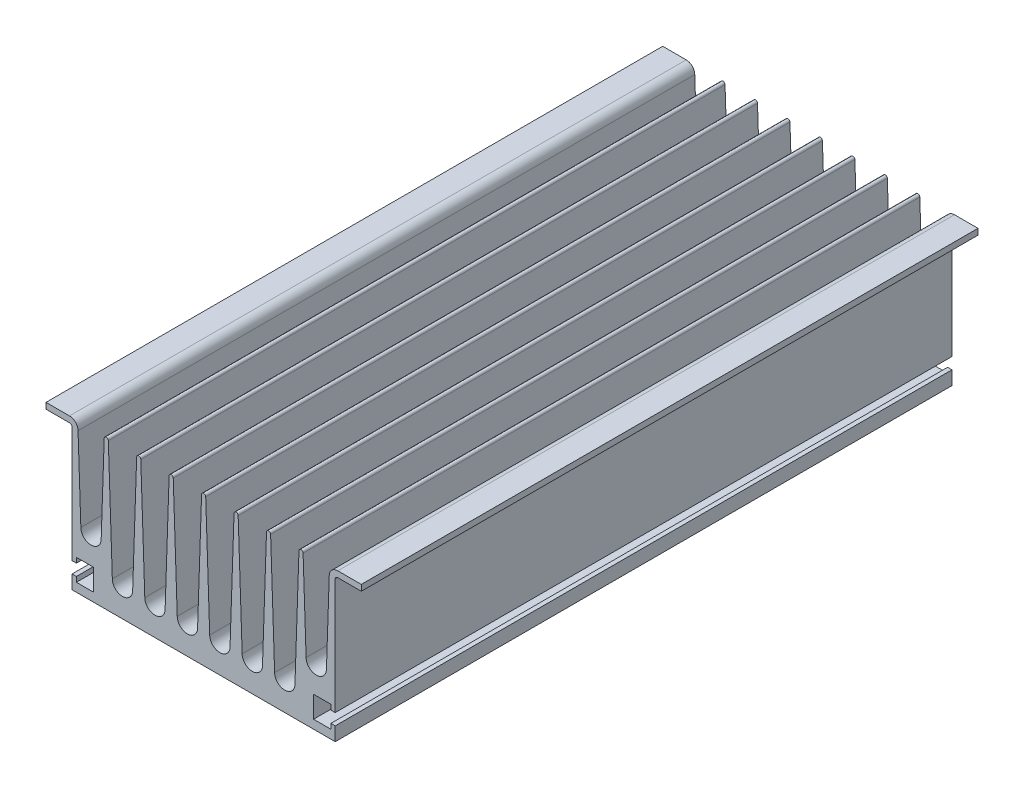
SolidWorks part; units mm, degrees
ref_plane "Plano frontal" through (0, 0, 0) normal (0, 0, 1) x (1, 0, 0)
ref_plane "Plano superior" through (0, 0, 0) normal (0, 1, 0) x (1, 0, 0)
ref_plane "Plano direito" through (0, 0, 0) normal (1, 0, 0) x (0, 0, -1)
sketch "Esboço1" plane through (0, 0, 0) normal (0, 0, 1) x (1, 0, 0)
  line L3 (0, 0) -> (-121.6, 0)
  line L47 (-121.6, 0) -> (-121.6, 6.35)
  line L49 (-121.6, 6.35) -> (-119.6, 6.35)
  line L51 (-119.6, 6.35) -> (-119.6, 4)
  line L53 (-119.6, 4) -> (-111.6, 4)
  line L55 (-111.6, 4) -> (-111.6, 14)
  line L57 (-111.6, 14) -> (-119.6, 14)
  line L61 (-119.6, 14) -> (-119.6, 11.65)
  line L65 (-119.6, 11.65) -> (-121.6, 11.65)
  line L97 (-121.6, 11.65) -> (-121.6, 65.056)
  line L98 (-122.7867, 66.2427) -> (-133.65, 66.2427)
  line L100 (-133.65, 66.2427) -> (-133.65, 69)
  line L101 (-133.65, 69) -> (-122.7867, 69)
  line L102 (-115.6, 14) -> (-115.6, 4) construction
  line L103 (-119.6, 11.65) -> (-119.6, 6.35) construction
  line L104 (-119.6, 9) -> (-115.6, 9) construction
  line L113 (-117.5473, 27) -> (-118.8427, 65.056)
  line L114 (-117.5473, 27) -> (-108.1473, 27) construction
  line L115 (-60.8, 0) -> (-60.8, 69) construction
  line L116 (-133.65, 69) -> (9.4418, 69) construction
  line L146 (-108.1473, 27) -> (-106.75, 68.05)
  line L147 (-104.85, 68.05) -> (-103, 13.7)
  line L148 (-106.75, 68.05) -> (-104.85, 68.05) construction
  line L149 (-122.7867, 66.2427) -> (-122.7867, 69) construction
  line L150 (-121.6, 65.056) -> (-118.8427, 65.056) construction
  line L151 (-105.8, 68.05) -> (-105.8, 0) construction
  line L152 (-105.8, 27) -> (-103.4527, 27) construction
  line L153 (-105.8, 27) -> (-108.1473, 27) construction
  line L154 (-93.6, 13.7) -> (-103, 13.7) construction
  line L155 (-93.6, 13.7) -> (-91.75, 68.05)
  line L156 (-89.85, 68.05) -> (-88, 13.7)
  line L161 (-91.75, 68.05) -> (-89.85, 68.05) construction
  line L162 (-78.6, 13.7) -> (-76.75, 68.05)
  line L163 (-88, 13.7) -> (-78.6, 13.7) construction
  line L164 (-76.75, 68.05) -> (-74.85, 68.05) construction
  line L165 (-74.85, 68.05) -> (-73, 13.7)
  line L166 (-63.6, 13.7) -> (-61.75, 68.05)
  line L167 (-61.75, 68.05) -> (-59.85, 68.05) construction
  line L168 (-73, 13.7) -> (-63.6, 13.7) construction
  line L169 (-122.7867, 66.2427) -> (-122.7867, 65.056) construction
  line L170 (-122.7867, 65.056) -> (-121.6, 65.056) construction
  line L171 (0, 0) -> (0, 6.35)
  line L172 (1.1867, 65.056) -> (0, 65.056) construction
  line L173 (1.1867, 66.2427) -> (1.1867, 65.056) construction
  line L174 (-48.6, 13.7) -> (-58, 13.7) construction
  line L175 (-44.85, 68.05) -> (-46.75, 68.05) construction
  line L176 (-33.6, 13.7) -> (-43, 13.7) construction
  line L177 (-29.85, 68.05) -> (-31.75, 68.05) construction
  line L178 (-28, 13.7) -> (-18.6, 13.7) construction
  line L179 (-15.8, 27) -> (-13.4527, 27) construction
  line L180 (-15.8, 27) -> (-18.1473, 27) construction
  line L181 (0, 65.056) -> (-2.7573, 65.056) construction
  line L182 (1.1867, 66.2427) -> (1.1867, 69) construction
  line L183 (-14.85, 68.05) -> (-16.75, 68.05) construction
  line L184 (-4.0527, 27) -> (-13.4527, 27) construction
  line L185 (-2, 9) -> (-6, 9) construction
  line L186 (-2, 11.65) -> (-2, 6.35) construction
  line L187 (-6, 14) -> (-6, 4) construction
  line L188 (-58, 13.7) -> (-59.85, 68.05)
  line L189 (-46.75, 68.05) -> (-48.6, 13.7)
  line L190 (-43, 13.7) -> (-44.85, 68.05)
  line L191 (-31.75, 68.05) -> (-33.6, 13.7)
  line L192 (-28, 13.7) -> (-29.85, 68.05)
  line L193 (-16.75, 68.05) -> (-18.6, 13.7)
  line L194 (-13.4527, 27) -> (-14.85, 68.05)
  line L195 (-4.0527, 27) -> (-2.7573, 65.056)
  line L196 (12.05, 69) -> (1.1867, 69)
  line L197 (12.05, 66.2427) -> (12.05, 69)
  line L198 (1.1867, 66.2427) -> (12.05, 66.2427)
  line L199 (0, 11.65) -> (0, 65.056)
  line L200 (-2, 11.65) -> (0, 11.65)
  line L201 (-2, 14) -> (-2, 11.65)
  line L202 (-10, 14) -> (-2, 14)
  line L203 (-10, 4) -> (-10, 14)
  line L204 (-2, 4) -> (-10, 4)
  line L205 (-2, 6.35) -> (-2, 4)
  line L206 (0, 6.35) -> (-2, 6.35)
  arc A1 (-121.6, 65.056) -> (-122.7867, 66.2427) centre (-122.7867, 65.056) ccw
  arc A2 (-118.8427, 65.056) -> (-122.7867, 69) centre (-122.7867, 65.056) ccw
  arc A3 (-117.5473, 27) -> (-108.1473, 27) centre (-112.8473, 27) ccw
  arc A4 (-106.75, 68.05) -> (-104.85, 68.05) centre (-105.8, 68.05) cw
  arc A5 (-93.6, 13.7) -> (-103, 13.7) centre (-98.3, 13.7) cw
  arc A6 (-91.75, 68.05) -> (-89.85, 68.05) centre (-90.8, 68.05) cw
  arc A7 (-88, 13.7) -> (-78.6, 13.7) centre (-83.3, 13.7) ccw
  arc A8 (-76.75, 68.05) -> (-74.85, 68.05) centre (-75.8, 68.05) cw
  arc A9 (-59.85, 68.05) -> (-61.75, 68.05) centre (-60.8, 68.05) ccw
  arc A10 (-73, 13.7) -> (-63.6, 13.7) centre (-68.3, 13.7) ccw
  arc A11 (-48.6, 13.7) -> (-58, 13.7) centre (-53.3, 13.7) cw
  arc A12 (-44.85, 68.05) -> (-46.75, 68.05) centre (-45.8, 68.05) ccw
  arc A13 (-33.6, 13.7) -> (-43, 13.7) centre (-38.3, 13.7) cw
  arc A14 (-29.85, 68.05) -> (-31.75, 68.05) centre (-30.8, 68.05) ccw
  arc A15 (-28, 13.7) -> (-18.6, 13.7) centre (-23.3, 13.7) ccw
  arc A16 (-14.85, 68.05) -> (-16.75, 68.05) centre (-15.8, 68.05) ccw
  arc A17 (-4.0527, 27) -> (-13.4527, 27) centre (-8.7527, 27) cw
  arc A18 (-2.7573, 65.056) -> (1.1867, 69) centre (1.1867, 65.056) cw
  arc A19 (0, 65.056) -> (1.1867, 66.2427) centre (1.1867, 65.056) cw
  point P24 (-123.4226, 69.701)
  point P43 (-118.817, 64.3035)
  point P50 (-88, 13.7)
  point P55 (-133.65, 67.6213)
  point P56 (-123.5004, 69.988)
  point P57 (0, 0)
  dimension "D7" = 42
  dimension "D9" = 4.7
  dimension "D10" = 13.7
  dimension "D11" = 72.85
  dimension "D15" = 4.7
  dimension "D13" = 10.8633
  dimension "D1" = 5.3
  dimension "D2" = 9
  dimension "D3" = 121.6
  dimension "D4" = 8
  dimension "D5" = 10
  dimension "D6" = 2
  dimension "D8" = 69
  dimension "D12" = 15
  dimension "D14" = 13.1
extrude "Ressalto-extrusão1" add sketch "Esboço1" along normal blind 285
sketch "Esboço2" [suppressed] plane through (0, 0, 0) normal (0, 0, -1) x (-1, 0, 0)
  line L1 (-155, 59) -> (0, 59) construction
  line L2 (-124.5538, 57.2679) -> (-123.5538, 59) construction
  line L3 (-125.5538, 55.5359) -> (-132.0538, 44.2776)
  line L4 (-132.0538, 44.2776) -> (-123.3936, 39.2776)
  line L5 (-123.3936, 39.2776) -> (-123.3936, -2.1816)
  line L6 (-123.3936, -2.1816) -> (-157.2094, -2.1816)
  line L7 (-157.2094, -2.1816) -> (-157.2094, 65.2148)
  line L8 (-157.2094, 65.2148) -> (-123.5538, 65.2148)
  line L9 (-123.5538, 65.2148) -> (-123.5538, 59)
  line L10 (-31.4462, 59) -> (7.5297, 59)
  line L11 (-31.4462, 59) -> (-30.4462, 57.2679) construction
  line L12 (7.5297, 59) -> (7.5297, -3.4441)
  line L13 (7.5297, -3.4441) -> (-31.6064, -3.4441)
  line L14 (-31.6064, -3.4441) -> (-31.6064, 39.2776)
  line L15 (-34.1064, 43.6077) -> (-31.6064, 39.2776) construction
  line L16 (-31.6064, 39.2776) -> (-22.9462, 44.2776)
  line L17 (-22.9462, 44.2776) -> (-29.4462, 55.5359)
  line L18 (-29.4462, 55.5359) -> (-27.7141, 56.5359)
  line L19 (-27.7141, 56.5359) -> (-28.7141, 58.2679)
  line L20 (-28.7141, 58.2679) -> (-30.4462, 57.2679)
  line L21 (-30.4462, 57.2679) -> (-31.4462, 59)
  line L22 (-128.75, 50) -> (-125.5538, 55.5359) construction
  line L23 (-125.5538, 55.5359) -> (-122.5228, 53.7859)
  line L24 (-122.5228, 53.7859) -> (-121.5228, 55.5179)
  line L25 (-121.5228, 55.5179) -> (-124.5538, 57.2679)
  line L26 (-124.5538, 57.2679) -> (-121.5228, 55.5179) construction
  line L27 (-124.5538, 57.2679) -> (-123.5538, 59)
extrude "Corte-extrusão1" [suppressed] cut sketch "Esboço2" against normal through all both and the other way through all
sketch "Esboço3" [suppressed] plane through (0, 0, 285) normal (0, 0, 1) x (1, 0, 0)
  circle A0 centre (47.5, 53.5) radius 1.25
  circle A1 centre (107.5, 53.5) radius 1.25
  dimension "D1" = 2.5
  dimension "D2" = 2.5
extrude "Corte-extrusão2" [suppressed] cut sketch "Esboço3" against normal blind 10
sketch "Esboço4" [suppressed] plane through (9.615, -2.5557, 0) normal (1, 0, 0) x (0, 0, -1)
  line L0 (-285, 57.5557) -> (-283.5, 57.5557)
  line L1 (-283.5, 57.5557) -> (-283.5, 59.5557)
  line L2 (-283.5, 59.5557) -> (-285, 59.5557)
  line L3 (-285, 59.5557) -> (-285, 57.5557)
  line L4 (-285, 60.8237) -> (-285, 59.0916) construction
extrude "Corte-extrusão3" [suppressed] cut sketch "Esboço4" against normal through all both and the other way through all
sketch "Esboço5" [suppressed] plane through (-1.9631, 1.1334, 0) normal (-0.866, 0.5, 0) x (0, 0, 1)
  circle A0 centre (45, 54.8186) radius 1.65
  circle A1 centre (275, 54.8186) radius 1.65
  dimension "D1" = 3.3
extrude "Corte-extrusão4" [suppressed] cut sketch "Esboço5" against normal blind 10
sketch "Esboço6" [suppressed] plane through (118.2131, 68.2504, 0) normal (0.866, 0.5, 0) x (0, 0, -1)
  circle A0 centre (-275, -22.6814) radius 2.25
  circle A1 centre (-45, -22.6814) radius 2.25
  dimension "D1" = 4.5
extrude "Corte-extrusão5" [suppressed] cut sketch "Esboço6" against normal through all both and the other way through all
sketch "Esboço8" [suppressed] plane through (118.2131, 68.2504, 0) normal (0.866, 0.5, 0) x (0, 0, -1)
  circle A0 centre (-275, -22.6814) radius 6
  circle A1 centre (-45, -22.6814) radius 6
  dimension "D1" = 12
extrude "Corte-extrusão6" [suppressed] cut sketch "Esboço8" against normal blind 100 from offset 4 offset against normal yes
